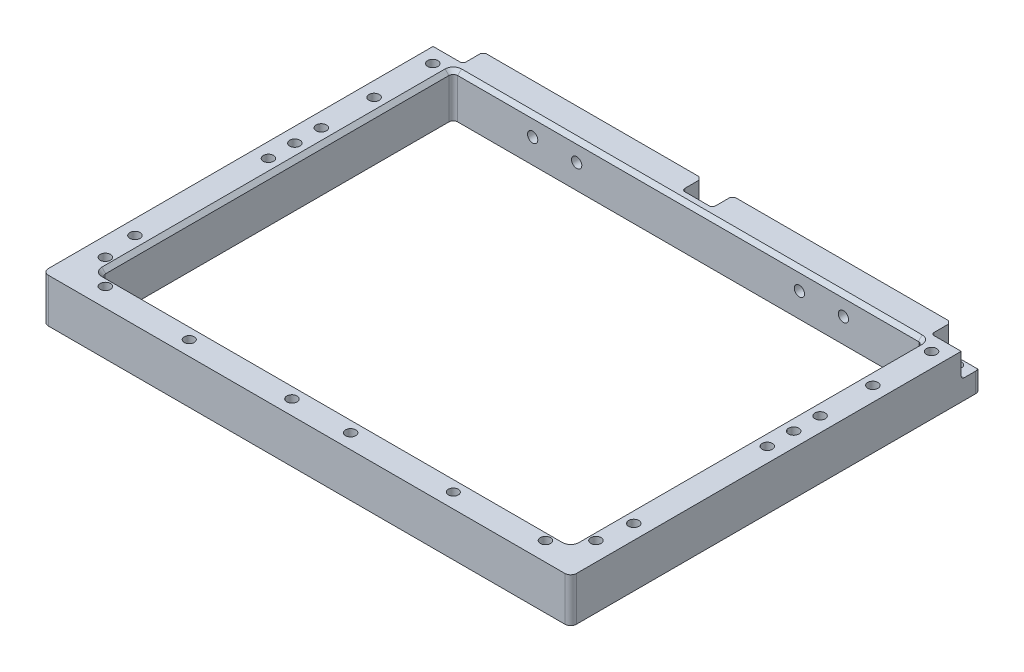
SolidWorks part; units mm, degrees
material "PLA"
ref_plane "Front Plane" through (0, 0, 0) normal (0, 0, 1) x (1, 0, 0)
ref_plane "Top Plane" through (0, 0, 0) normal (0, 1, 0) x (1, 0, 0)
ref_plane "Right Plane" through (0, 0, 0) normal (1, 0, 0) x (0, 0, -1)
sketch "Sketch1" plane through (0, 0, 0) normal (0, 1, 0) x (1, 0, 0)
  line L1 (-114.3, 88.9) -> (114.3, 88.9)
  line L2 (-114.3, 88.9) -> (-114.3, -88.9)
  line L3 (-114.3, -88.9) -> (114.3, -88.9)
  line L4 (114.3, 88.9) -> (114.3, -88.9)
  line L5 (-114.3, 88.9) -> (114.3, -88.9) construction
  line L6 (-114.3, -88.9) -> (114.3, 88.9) construction
  line L7 (-101.6, 76.2) -> (101.6, 76.2)
  line L8 (-101.6, 76.2) -> (-101.6, -76.2)
  line L9 (-101.6, -76.2) -> (101.6, -76.2)
  line L10 (101.6, 76.2) -> (101.6, -76.2)
  line L11 (-101.6, 76.2) -> (101.6, -76.2) construction
  line L12 (-101.6, -76.2) -> (101.6, 76.2) construction
  point P0 (0, 0)
  point P6 (0, 0)
  dimension "D1" = 177.8
  dimension "D2" = 152.4
  dimension "D3" = 228.6
  dimension "D4" = 203.2
extrude "Boss-Extrude1" add sketch "Sketch1" along normal blind 19.05
sketch "Sketch2" plane through (0, 0, -88.9) normal (0, 0, -1) x (-1, 0, 0)
  line L0 (114.3, 19.05) -> (114.3, 8.509)
  line L1 (114.3, 19.05) -> (114.3, 0) construction
  line L2 (114.3, 8.509) -> (101.346, 8.509)
  line L3 (101.346, 8.509) -> (101.346, 19.05)
  line L4 (-114.3, 19.05) -> (114.3, 19.05) construction
  line L5 (101.346, 19.05) -> (114.3, 19.05)
  line L6 (0, 0) -> (0, 19.05) construction
  line L7 (-6.604, 19.05) -> (6.604, 19.05)
  line L8 (6.604, 19.05) -> (6.604, 8.509)
  line L9 (6.604, 8.509) -> (-6.604, 8.509)
  line L11 (-6.604, 19.05) -> (-6.604, 8.509)
  line L12 (-101.346, 19.05) -> (-114.3, 19.05)
  line L13 (-101.346, 8.509) -> (-101.346, 19.05)
  line L14 (-114.3, 8.509) -> (-101.346, 8.509)
  line L15 (-114.3, 19.05) -> (-114.3, 8.509)
  point P16 (0, 8.509)
  dimension "D1" = 10.541
  dimension "D2" = 12.954
  dimension "D3" = 10.541
  dimension "D4" = 13.208
extrude "Cut-Extrude1" cut sketch "Sketch2" against normal blind 8.763
sketch "Sketch3" plane through (0, 8.509, 0) normal (0, 1, 0) x (1, 0, 0)
  line L0 (0, 88.9) -> (0, 80.137) construction
  line L1 (6.604, 88.9) -> (-6.604, 88.9) construction
  line L2 (-6.604, 80.137) -> (6.604, 80.137) construction
  line L3 (-107.823, 80.137) -> (-107.823, 88.9) construction
  line L4 (-114.3, 80.137) -> (-101.346, 80.137) construction
  line L5 (-101.346, 88.9) -> (-114.3, 88.9) construction
  circle A0 centre (-107.823, 84.5185) radius 2.2225
  circle A1 centre (0, 84.5185) radius 2.2225
  circle A2 centre (107.823, 84.5185) radius 2.2225
  dimension "D1" = 4.445
  dimension "D2" = 4.445
extrude "Front-Base-MountHoles" cut sketch "Sketch3" against normal blind 7.112
fillet "Fillet2" radius 1.27 11 edges at (101.346, 8.509, -84.5185) (107.823, 8.509, -80.137) (-6.604, 8.509, -84.5185) (0, 8.509, -80.137) (6.604, 8.509, -84.5185) (-107.823, 8.509, -80.137) (-101.346, 8.509, -84.5185) (-101.346, 13.7795, -80.137) (-6.604, 13.7795, -80.137) (6.604, 13.7795, -80.137) (101.346, 13.7795, -80.137)
chamfer "Chamfer1" distance 1.27 angle 45 11 edges at (-108.458, 8.509, -88.9) (-101.718, 8.881, -88.9) (-101.346, 14.4145, -88.9) (-6.604, 14.4145, -88.9) (-6.232, 8.881, -88.9) (0, 8.509, -88.9) (6.232, 8.881, -88.9) (6.604, 14.4145, -88.9) (108.458, 8.509, -88.9) (101.718, 8.881, -88.9) (101.346, 14.4145, -88.9)
sketch "Sketch4" plane through (0, 0, -88.9) normal (0, 0, -1) x (-1, 0, 0)
  line L0 (0, 0) -> (0, 19.05) construction
  line L1 (-114.3, 0) -> (114.3, 0) construction
  line L2 (5.334, 19.05) -> (-5.334, 19.05) construction
  circle A0 centre (-20.32, 9.525) radius 2.2225
  circle A1 centre (-81.28, 9.525) radius 2.2225
  circle A2 centre (81.28, 9.525) radius 2.2225
  circle A3 centre (20.32, 9.525) radius 2.2225
  dimension "D1" = 4.445
  dimension "D2" = 4.445
  dimension "D4" = 81.28
  dimension "D5" = 9.525
  dimension "D6" = 9.525
extrude "Front-base-MountHoles2" cut sketch "Sketch4" against normal blind 7.62
sketch "Sketch5" plane through (0, 19.05, 0) normal (0, 1, 0) x (1, 0, 0)
  line L0 (-114.3, 80.137) -> (-114.3, -88.9) construction
  line L1 (-114.3, -88.9) -> (114.3, -88.9) construction
  line L2 (0, 0) -> (0, -50000) construction
  circle A0 centre (-95.25, -80.772) radius 2.2225
  circle A1 centre (-106.172, -69.85) radius 2.2225
  circle A2 centre (106.172, -69.85) radius 2.2225
  circle A3 centre (95.25, -80.772) radius 2.2225
  dimension "D1" = 4.445
  dimension "D2" = 4.445
  dimension "D3" = 8.128
  dimension "D4" = 8.128
  dimension "D5" = 19.05
  dimension "D6" = 19.05
extrude "Rear-Wall-MountHoles" cut sketch "Sketch5" against normal blind 7.62
fillet "Fillet3" radius 1.905 4 edges at (-101.6, 9.525, 76.2) (101.6, 9.525, 76.2) (101.6, 9.525, -76.2) (-101.6, 9.525, -76.2)
sketch "Sketch6" plane through (0, 19.05, 0) normal (0, 1, 0) x (1, 0, 0)
  line L0 (114.3, -88.9) -> (114.3, 80.137) construction
  line L1 (-99.695, -76.2) -> (99.695, -76.2) construction
  line L2 (101.6, -74.295) -> (101.6, 74.295) construction
  line L3 (0, 0) -> (0, -76.2) construction
  circle A0 centre (107.95, -55.245) radius 2.2225
  circle A1 centre (107.95, 2.54) radius 2.2225
  circle A2 centre (107.95, 13.97) radius 2.2225
  circle A3 centre (107.95, 25.4) radius 2.2225
  circle A8 centre (-107.95, 25.4) radius 2.2225
  circle A9 centre (-107.95, 13.97) radius 2.2225
  circle A10 centre (-107.95, 2.54) radius 2.2225
  circle A11 centre (-107.95, -55.245) radius 2.2225
  dimension "D1" = 4.445
  dimension "D4" = 4.445
  dimension "D5" = 4.445
  dimension "D6" = 4.445
  dimension "D2" = 6.35
  dimension "D3" = 20.955
  dimension "D7" = 78.74
  dimension "D8" = 90.17
  dimension "D9" = 101.6
  dimension "D10" = 6.35
  dimension "D11" = 6.35
  dimension "D12" = 6.35
extrude "Motor_Mount_Holes" cut sketch "Sketch6" against normal blind 7.62
chamfer "Chamfer2" distance 1.651 angle 45 8 edges at (-101.6, 19.05, 0) (-101.042, 19.05, 75.642) (-101.042, 19.05, -75.642) (0, 19.05, 76.2) (0, 19.05, -76.2) (101.042, 19.05, 75.642) (101.042, 19.05, -75.642) (101.6, 19.05, 0)
sketch "Sketch7" plane through (0, 19.05, 0) normal (0, 1, 0) x (1, 0, 0)
  line L0 (0, 0) -> (0, -88.9) construction
  line L1 (-114.3, -88.9) -> (114.3, -88.9) construction
  line L2 (-12.7, -76.2) -> (-12.7, -88.9) construction
  line L4 (-99.695, -76.2) -> (99.695, -76.2) construction
  circle A0 centre (-12.7, -82.55) radius 2.2225
  circle A1 centre (12.7, -82.55) radius 2.2225
  dimension "D1" = 4.445
  dimension "D2" = 12.7
extrude "RearBrace_MountHoles" cut sketch "Sketch7" against normal blind 7.62
sketch "Sketch8" plane through (0, 19.05, 0) normal (0, 1, 0) x (1, 0, 0)
  line L0 (114.3, 60.96) -> (101.6, 60.96) construction
  line L1 (114.3, -88.9) -> (114.3, 80.137) construction
  line L2 (101.6, -74.295) -> (101.6, 74.295) construction
  line L3 (107.95, 60.96) -> (107.95, 73.66) construction
  line L4 (-99.695, -76.2) -> (99.695, -76.2) construction
  line L5 (0, 0) -> (0, -88.9) construction
  line L6 (-114.3, -88.9) -> (114.3, -88.9) construction
  line L7 (-107.95, 60.96) -> (-107.95, 73.66) construction
  line L8 (-114.3, 60.96) -> (-101.6, 60.96) construction
  circle A0 centre (107.95, 73.66) radius 2.2225
  circle A1 centre (107.95, 48.26) radius 2.2225
  circle A2 centre (-107.95, 48.26) radius 2.2225
  circle A3 centre (-107.95, 73.66) radius 2.2225
  dimension "D1" = 4.445
  dimension "D2" = 25.4
  dimension "D3" = 137.16
extrude "SideBrace_MountHoles" cut sketch "Sketch8" against normal blind 7.112
sketch "Sketch9" plane through (0, 19.05, 0) normal (0, 1, 0) x (1, 0, 0)
  line L0 (0, -88.9) -> (0, -76.2) construction
  line L1 (-114.3, -88.9) -> (114.3, -88.9) construction
  line L2 (-99.695, -76.2) -> (99.695, -76.2) construction
  line L3 (0, -82.55) -> (-57.15, -82.55) construction
  circle A0 centre (-57.15, -82.55) radius 2.159
  circle A1 centre (57.15, -82.55) radius 2.159
  dimension "D1" = 4.318
  dimension "D2" = 114.3
extrude "BatteryMount_Holes" cut sketch "Sketch9" against normal blind 8.89
fillet "Fillet4" radius 2.54 4 edges at (-114.3, 3.6195, -88.9) (114.3, 3.6195, -88.9) (-114.3, 9.525, 88.9) (114.3, 9.525, 88.9)
sketch "Sketch10" plane through (0, 0, -76.2) normal (0, 0, 1) x (1, 0, 0)
  line L0 (0, 0) -> (0, 50000) construction
  line L1 (-111.76, 0) -> (111.76, 0) construction
  line L2 (101.6, 17.399) -> (101.6, 0) construction
  line L3 (48.2067, 10.541) -> (67.2567, 10.541) construction
  line L4 (99.695, 0) -> (-99.695, 0) construction
  line L5 (-48.2067, 10.541) -> (-67.2567, 10.541) construction
  circle A0 centre (48.2067, 10.541) radius 2.2225
  circle A1 centre (67.2567, 10.541) radius 2.2225
  circle A2 centre (-67.2567, 10.541) radius 2.2225
  circle A3 centre (-48.2067, 10.541) radius 2.2225
  point P4 (0, 0)
  dimension "D3" = 4.445
  dimension "D1" = 19.05
  dimension "D2" = 34.3433
  dimension "D4" = 10.541
extrude "Motor-Brace-MountHoles" cut sketch "Sketch10" against normal blind 5.588
equation "\"D2@Sketch3\"=\"D1@Sketch3\""
equation "\"D2@Sketch5\"=\"D1@Sketch5\""
equation "\"D4@Sketch6\"=\"D1@Sketch6\""
equation "\"D5@Sketch6\"=\"D1@Sketch6\""
equation "\"D6@Sketch6\"=\"D1@Sketch6\""
equation "\"D10@Sketch6\"=\"D2@Sketch6\""
equation "\"D11@Sketch6\"=\"D2@Sketch6\""
equation "\"D12@Sketch6\"=\"D2@Sketch6\""
equation "\"D1@Sketch2\"=\"D3@Sketch2\""
equation "\"D1@Sketch4\"=\"D2@Sketch4\""
